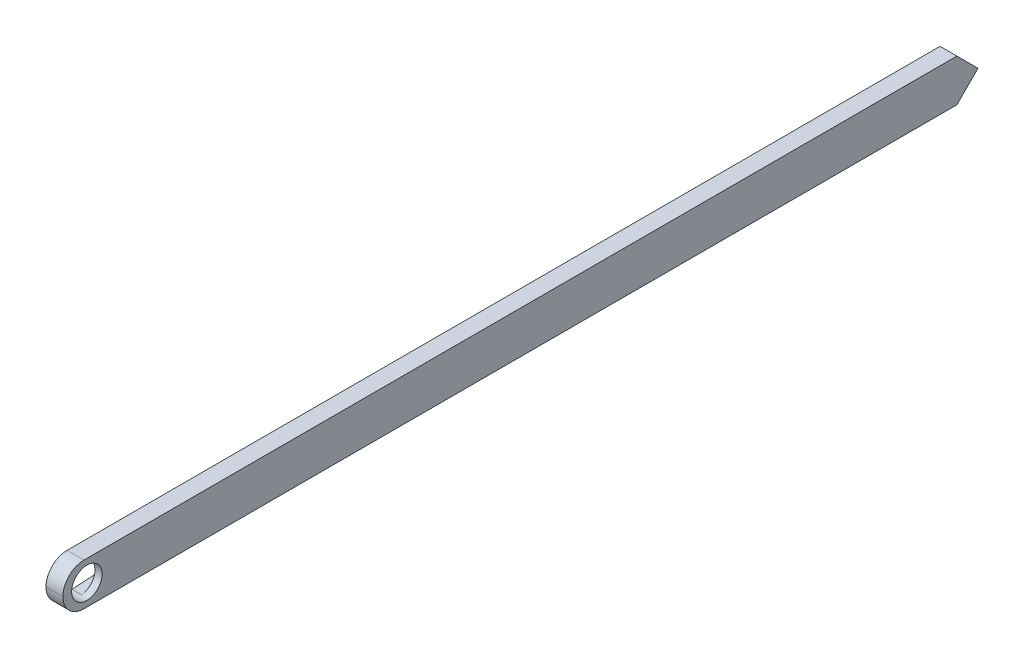
SolidWorks part; units mm, degrees
material "Custom Plastic"
ref_plane "Front Plane" through (0, 0, 0) normal (0, 0, 1) x (1, 0, 0)
ref_plane "Top Plane" through (0, 0, 0) normal (0, 1, 0) x (1, 0, 0)
ref_plane "Right Plane" through (0, 0, 0) normal (1, 0, 0) x (0, 0, -1)
sketch "Sketch1" plane through (0, 0, 0) normal (1, 0, 0) x (0, 0, -1)
  line L1 (0, 0) -> (191.86, 0)
  line L2 (0, 0) -> (0, 10)
  line L3 (0, 10) -> (191.86, 10)
  line L6 (191.86, 0) -> (191.86, 10)
  line L7 (191.86, 10) -> (211.86, 10)
  line L8 (211.86, 10) -> (216.86, 5)
  line L9 (216.86, 5) -> (211.86, 0)
  line L10 (211.86, 0) -> (191.86, 0)
  point P6 (191.86, 5)
  dimension "D2" = 10
  dimension "D3" = 191.86
  dimension "D1" = 20
  dimension "D4" = 5
extrude "Boss-Extrude1" add sketch "Sketch1" along normal blind 4 contours L1 L6 L3 L2 | L10 L9 L8 L7 L6 region at (0, 5, -95.93) region at (0, 5, -203.1563)
sketch "Sketch7" plane through (0, 0, 0) normal (-1, 0, 0) x (0, 0, 1)
  line L0 (-6.154, 8.58) -> (-23.2274, 7.505)
  line L1 (-23.2274, 2.495) -> (-6.154, 1.42)
  line L2 (0, 0) -> (0, 10) construction
  line L3 (0, 10) -> (-211.86, 10) construction
  line L4 (-191.86, 0) -> (-191.86, 10) construction
  line L5 (0, 0) -> (-211.86, 0) construction
  circle A0 centre (-5.6896, 5) radius 3.61
  arc A1 (-23.2274, 7.505) -> (-23.2274, 2.495) centre (-23.0696, 5) ccw
  point P6 (0, 5)
  point P8 (-5.6896, 5)
  dimension "D1" = 7.22
  dimension "D2" = 7.16
  dimension "D3" = 186.1704
  dimension "D6" = 20
  dimension "D4" = 23.5
  dimension "D5" = 5.01
extrude "Cut-Extrude1" cut sketch "Sketch7" against normal through all contours A0 region at (0, 5, -5.6896)
extrude "Cut-Extrude2" cut sketch "Sketch7<3>" against normal offset from surface (2.3 mm away) 1.7 contours L0 A1 L1 A0 region at (0, 5, -16.3399) up to face at (4, 5, -2.0796)
sketch "Sketch7<3>" plane through (0, 0, 0) normal (-1, 0, 0) x (0, 0, 1) same geometry as "Sketch7"
fillet "Fillet1" radius 5 2 edges at (2, 10, 0) (2, 0, 0)
fillet "Fillet2" radius 2 2 edges at (1.15, 1.42, -6.154) (1.15, 8.58, -6.154)
mirror "Mirror1" [suppressed] of bodies 107
delete or keep bodies "Body-Delete/Keep 1" [suppressed] type delete bodies bodies 107
equation "\"D3@Sketch7\"=3.676in+2in+42mm"
equation "\"D3@Sketch1\"=99.06mm+2in+42mm"
